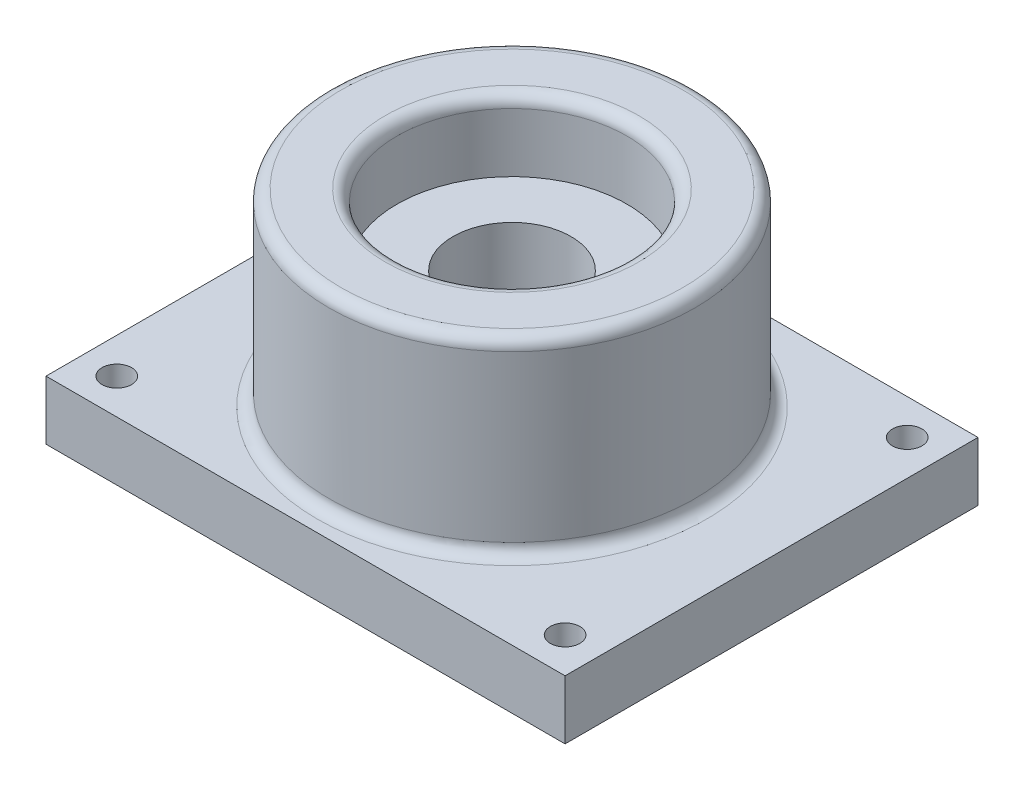
SolidWorks part; units mm, degrees
ref_plane "Front Plane" through (0, 0, 0) normal (0, 0, 1) x (1, 0, 0)
ref_plane "Top Plane" through (0, 0, 0) normal (0, 1, 0) x (1, 0, 0)
ref_plane "Right Plane" through (0, 0, 0) normal (1, 0, 0) x (0, 0, -1)
sketch "Sketch1" plane through (0, 0, 0) normal (0, 1, 0) x (1, 0, 0)
  circle A0 centre (0, 0) radius 15.5
  dimension "D1" = 31
extrude "Boss-Extrude1" add sketch "Sketch1" along normal blind 16
ref_plane "Plane1" through (0, 0, 0) normal (0, -1, 0) x (-1, 0, 0)
sketch "Sketch16" plane through (0, 0, 0) normal (0, -1, 0) x (1, 0, 0)
  line L0 (0, 0) -> (22, 17.5) construction
  line L1 (-22, 17.5) -> (22, 17.5)
  line L2 (-22, 17.5) -> (-22, -17.5)
  line L3 (-22, -17.5) -> (22, -17.5)
  line L4 (22, 17.5) -> (22, -17.5)
  line L5 (-22, 17.5) -> (22, -17.5) construction
  circle A3 centre (-19, 14.5) radius 1.25
  circle A6 centre (19, 14.5) radius 1.25
  circle A7 centre (19, -14.5) radius 1.25
  circle A8 centre (-19, -14.5) radius 1.25
  point P0 (0, 0)
  dimension "D3" = 2
  dimension "D5" = 2.5
  dimension "D8" = 3
  dimension "D1" = 35
  dimension "D2" = 44
  dimension "D4" = 2
  dimension "D9" = 3
extrude "Boss-Extrude6" add sketch "Sketch16" along normal blind 5
sketch "Sketch17" plane through (0, 16, 0) normal (0, 1, 0) x (1, 0, 0)
  circle A0 centre (0, 0) radius 9.75
  dimension "D1" = 19.5
extrude "Cut-Extrude5" cut sketch "Sketch17" against normal blind 6
sketch "Sketch18" plane through (0, 10, 0) normal (0, 1, 0) x (1, 0, 0)
  circle A0 centre (0, 0) radius 5
  dimension "D1" = 10
extrude "Cut-Extrude7" cut sketch "Sketch18" against normal blind 19
fillet "Fillet4" radius 1 1 edges at (0, 0, 15.5)
fillet "Fillet1" radius 1 1 edges at (0, 16, 9.75)
fillet "Fillet3" radius 1 1 edges at (0, 16, 15.5)
